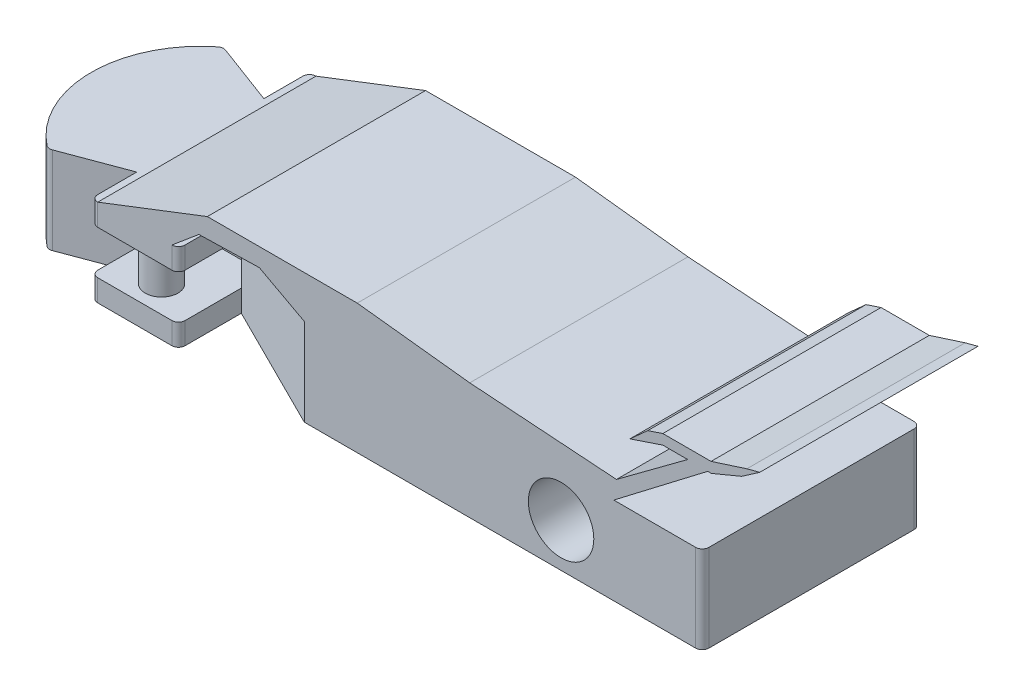
SolidWorks part; units mm, degrees
ref_plane "Front Plane" through (0, 0, 0) normal (0, 0, 1) x (1, 0, 0)
ref_plane "Top Plane" through (0, 0, 0) normal (0, 1, 0) x (1, 0, 0)
ref_plane "Right Plane" through (0, 0, 0) normal (1, 0, 0) x (0, 0, -1)
sketch "Sketch1" plane through (0, 0, 0) normal (0, 1, 0) x (1, 0, 0)
  line L0 (349.8123, 0) -> (-774.0001, 0) construction
  line L5 (-355.6, -127) -> (342.9, -127)
  line L6 (-355.6, -127) -> (-355.6, 127)
  line L7 (-355.6, 127) -> (342.9, 127)
  line L8 (355.6, -127) -> (355.6, 127)
  line L9 (-355.6, -127) -> (355.6, 127) construction
  line L10 (-355.6, 127) -> (355.6, -127) construction
  line L11 (-356.4221, 126.8299) -> (-355.6, 127)
  line L12 (-356.4221, -126.8299) -> (-355.6, -127)
  line L13 (342.9, -127) -> (355.6, -127)
  line L14 (-127, 127) -> (-127, -254) construction
  line L15 (-774.0001, 0) -> (-997.913, 0) construction
  line L17 (342.9, 127) -> (355.6, 127)
  arc A0 (-355.6, 127) -> (-355.6, -127) centre (-355.6, 0) ccw
  point P0 (0, 0)
  point P6 (-482.6, 0)
  dimension "D3" = 482.6
  dimension "D1" = 254
  dimension "D2" = 838.2
extrude "Boss-Extrude3" add sketch "Sketch1" along normal blind 101.6 contours A0 L6 | L7 L6 L5 L8 region at (0, 0, 0) region at (-409.5005, 0, 0)
sketch "Sketch4" plane through (0, 0, 127) normal (0, 0, 1) x (1, 0, 0)
  line L0 (-355.6, 101.6) -> (355.6, 101.6) construction
  line L1 (191.262, 50.8) -> (-376.5324, 46.2869) construction
  line L3 (355.6, 101.6) -> (355.6, 0) construction
  circle A0 centre (191.262, 50.8) radius 38.1
  dimension "D2" = 76.2
  dimension "D1" = 50.8
  dimension "D3" = 50.8
  dimension "D4" = 164.338
extrude "Cut-Extrude1" cut sketch "Sketch4" against normal blind 508 contours A0
sketch "Sketch16" plane through (0, 101.6, 0) normal (0, 1, 0) x (1, 0, 0)
  line L0 (0, 0) -> (0, 127) construction
  line L1 (-355.6, 127) -> (-254, 127)
  line L2 (-355.6, 127) -> (342.9, 127) construction
  line L3 (-355.6, -25.4) -> (-254, -25.4)
  line L4 (-355.6, -25.4) -> (-355.6, -127)
  line L5 (0, 127) -> (0, -127) construction
  line L6 (-355.6, -127) -> (342.9, -127) construction
  line L7 (355.6, 0) -> (-613.2028, 0) construction
  line L8 (355.6, -127) -> (355.6, 127) construction
  line L9 (349.8123, 0) -> (-774.0001, 0) construction
  line L10 (-355.6, 127) -> (-355.6, -127) construction
  line L15 (-254, 25.4) -> (-254, 127)
  line L24 (-355.6, -127) -> (-254, -127)
  line L25 (-254, -25.4) -> (-254, -127)
  line L26 (-355.6, 25.4) -> (-254, 25.4)
  line L27 (-355.6, 25.4) -> (-355.6, 127)
  dimension "D1" = 101.6
  dimension "D2" = 101.6
ref_plane "Plane3" through (0, 76.2, 0) normal (0, 1, 0) x (1, 0, 0)
extrude "Cut-Extrude2" cut sketch "Sketch16" against normal blind 50.8 from surface starting at plane "Plane3"
sketch "Sketch18" plane through (0, 25.4, 0) normal (0, 1, 0) x (1, 0, 0)
  line L1 (-355.6, -127) -> (-355.6, 127) construction
  line L3 (-482.6, 0) -> (349.8123, 0) construction
  line L4 (-355.6, -127) -> (-254, -127) construction
  line L5 (-304.8, -76.835) -> (-304.8, -25.4) construction
  line L7 (-355.6, -25.4) -> (-254, -25.4) construction
  circle A0 centre (-304.8, -95.885) radius 19.05
  arc A1 (-355.6, 127) -> (-355.6, -127) centre (-355.6, 0) ccw construction
  circle A2 centre (-304.8, 95.885) radius 19.05
  dimension "D3" = 38.1
  dimension "D1" = 31.115
  dimension "D2" = 50.8
extrude "Boss-Extrude4" add sketch "Sketch18" along normal blind 50.8
sketch "Sketch22" plane through (0, 0, 127) normal (0, 0, 1) x (1, 0, 0)
  line L0 (-292.1, 0) -> (-292.1, 102.484) construction
  line L1 (-355.6, 0) -> (355.6, 0) construction
  dimension "D1" = 63.5
sketch "Sketch23" plane through (0, 101.6, 0) normal (0, 1, 0) x (1, 0, 0)
  line L1 (-355.6, -127) -> (-355.6, -73.964)
  line L2 (-254, -53.8933) -> (-254, -127)
  line L3 (-254, -127) -> (-107.586, -127)
  line L4 (-613.2028, 0) -> (355.6, 0) construction
  line L9 (-355.6, 127) -> (-355.6, -127) construction
  line L13 (-127, 127) -> (-127, -127) construction
  line L15 (355.6, -127) -> (355.6, 127) construction
  line L18 (-355.6, -25.4) -> (-355.6, -127) construction
  line L19 (-355.6, -73.964) -> (-431.0292, -102.1735)
  line L20 (-355.6, 73.964) -> (-431.0292, 102.1735)
  line L21 (-355.6, 127) -> (-355.6, 73.964)
  line L23 (-254, -53.8933) -> (-107.586, -127)
  line L24 (-254, 127) -> (-107.586, 127)
  line L25 (-254, 53.8933) -> (-254, 127)
  line L26 (-254, 53.8933) -> (-107.586, 127)
  arc A0 (-431.0292, -102.1735) -> (-355.6, -127) centre (-355.6, 0) ccw
  arc A2 (-431.0292, 102.1735) -> (-355.6, 127) centre (-355.6, 0) cw
  dimension "D1" = 482.6
extrude "Cut-Extrude6" cut sketch "Sketch23" against normal blind 101.6
ref_plane "Plane4" through (0, 0, 127) normal (0, 0, 1) x (1, 0, 0)
fillet "Fillet2" radius 7.62 12 edges at (355.6, 50.8, 127) (355.6, 50.8, -127) (-254, 88.9, -127) (-254, 12.7, -127) (-355.6, 12.7, -127) (-355.6, 88.9, -127) (-431.0292, 50.8, -102.1735) (-431.0292, 50.8, 102.1735) (-254, 12.7, 127) (-254, 88.9, 127) (-355.6, 12.7, 127) (-355.6, 88.9, 127)
sketch "Sketch24" plane through (0, 0, 127) normal (0, 0, 1) x (1, 0, 0)
  line L19 (365.8279, 197.2104) -> (407.553, 210.6069)
  line L39 (355.6, 101.6) -> (-613.2028, 101.6) construction
  line L43 (338.6653, 185.506) -> (334.0871, 185.506)
  line L44 (334.0871, 185.506) -> (309.6864, 185.506)
  line L45 (309.6864, 197.2104) -> (292.1218, 191.3582)
  line L46 (309.6864, 197.2104) -> (365.8279, 197.2104)
  line L47 (338.6653, 185.506) -> (225.581, 101.6)
  line L49 (225.581, 101.6) -> (252.615, 101.6)
  line L50 (365.8279, 185.1093) -> (362.0586, 185.3076)
  line L51 (365.8279, 185.1093) -> (401.5362, 199.9597)
  line L52 (309.6864, 185.506) -> (271.3817, 172.6881)
  line L53 (271.3817, 172.6881) -> (292.1218, 191.3582)
  line L54 (401.5362, 199.9597) -> (422.4964, 214.5295)
  line L55 (422.4964, 214.5295) -> (407.553, 210.6069)
  line L56 (362.0586, 185.3076) -> (252.615, 101.6)
  line L66 (-347.98, 101.6) -> (-220.4456, 150.838)
  line L68 (-220.4456, 150.838) -> (-109.0542, 150.838)
  line L69 (-109.0542, 150.838) -> (-45.9644, 150.838)
  line L70 (-45.9644, 150.838) -> (84.982, 135.95)
  line L71 (255.7125, 123.9569) -> (225.581, 101.6)
  line L72 (-347.98, 101.6) -> (225.581, 101.6)
  line L73 (84.982, 135.95) -> (255.7125, 123.9569)
extrude "Boss-Extrude7" add sketch "Sketch24" against normal blind 254 separate body contours L56 L50 L51 L54 L55 L19 L46 L45 L53 L52 L44 L43 L47 L49 region at (314.1177, 162.9333, 127)
extrude "Boss-Extrude9" add sketch "Sketch24<8>" against normal blind 254 contours L73 L70 L69 L68 L66 L72 L47 region at (-53.9797, 122.1342, 127)
sketch "Sketch24<8>" plane through (0, 0, 127) normal (0, 0, 1) x (1, 0, 0) same geometry as "Sketch24"
sketch "Sketch26" plane through (0, 0, 127) normal (0, 0, 1) x (1, 0, 0)
  line L0 (-261.62, 101.6) -> (-230.279, 127.8792)
  line L1 (-230.279, 127.8792) -> (-159.925, 129.6303)
  line L2 (-159.925, 129.6303) -> (-107.586, 101.6)
  line L3 (-261.62, 101.6) -> (-107.586, 101.6) construction
  line L4 (-107.586, 101.6) -> (-261.62, 101.6)
extrude "Cut-Extrude11" cut sketch "Sketch26" against normal blind 50.8
sketch "Sketch27" plane through (0, 0, -127) normal (0, 0, -1) x (-1, 0, 0)
  line L0 (107.6067, 101.5906) -> (138.9477, 127.8698)
  line L1 (138.9477, 127.8698) -> (209.3017, 129.6209)
  line L2 (209.3017, 129.6209) -> (261.6407, 101.5906)
  line L3 (261.6407, 101.5906) -> (107.6067, 101.5906)
extrude "Cut-Extrude12" cut sketch "Sketch27" against normal blind 50.8
